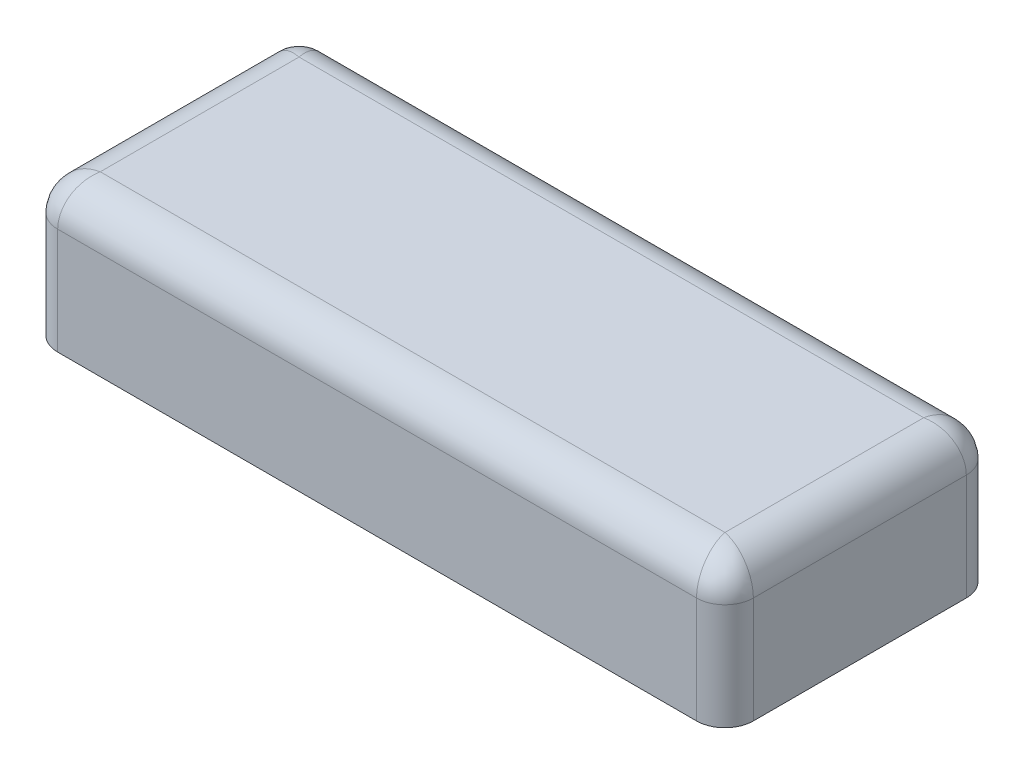
SolidWorks part; units mm, degrees
ref_plane "Front Plane" through (0, 0, 0) normal (0, 0, 1) x (1, 0, 0)
ref_plane "Top Plane" through (0, 0, 0) normal (0, 1, 0) x (1, 0, 0)
ref_plane "Right Plane" through (0, 0, 0) normal (1, 0, 0) x (0, 0, -1)
sketch "Sketch1" plane through (0, 0, 0) normal (0, 1, 0) x (1, 0, 0)
  line L0 (7.846, -6.2) -> (7.846, -6.2)
  line L1 (0.4, 0) -> (9.4, 0)
  line L2 (0, 0.4) -> (0, 3.4)
  line L3 (0.4, 3.8) -> (9.4, 3.8)
  line L4 (9.8, 0.4) -> (9.8, 3.4)
  line L5 (7.846, -6.2) -> (9.8, -6.2)
  line L6 (0, 3.8) -> (9.8, 3.8) construction
  line L7 (0, 0) -> (0, 3.8) construction
  arc A0 (9.4, 0) -> (9.8, 0.4) centre (9.4, 0.4) ccw
  arc A1 (9.4, 3.8) -> (9.8, 3.4) centre (9.4, 3.4) cw
  arc A2 (0.4, 0) -> (0, 0.4) centre (0.4, 0.4) cw
  arc A3 (0.4, 3.8) -> (0, 3.4) centre (0.4, 3.4) ccw
  point P10 (9.8, 0)
  point P14 (9.8, 3.8)
  point P18 (0, 0)
  point P22 (0, 0)
  point P23 (0, 0)
  dimension "D4" = 0.4
  dimension "D1" = 9
  dimension "D2" = 3.8
  dimension "D3" = 10
extrude "Boss-Extrude5" add sketch "Sketch1" along normal blind 2 contours L3 A3 L2 A2 L1 A0 L4 A1 region at (4.9, 0, -1.9)
fillet "Fillet2" radius 0.5 8 edges at (9.6828, 2, -3.6828) (9.8, 2, -1.9) (9.6828, 2, -0.1172) (4.9, 2, 0) (0.1172, 2, -0.1172) (0, 2, -1.9) (0.1172, 2, -3.6828) (4.9, 2, -3.8)
shell "Shell2" thickness 0.1 removed face at (4.9, 0, -1.9)
